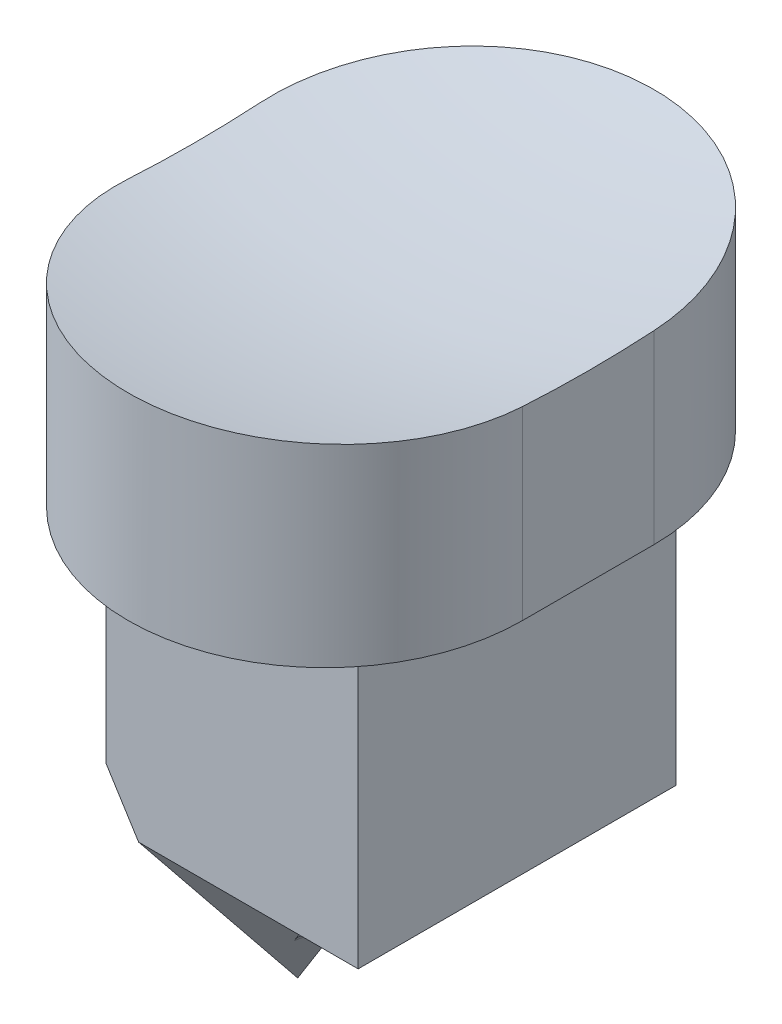
SolidWorks part; units mm, degrees
ref_plane "Front Plane" through (0, 0, 0) normal (0, 0, 1) x (1, 0, 0)
ref_plane "Top Plane" through (0, 0, 0) normal (0, 1, 0) x (1, 0, 0)
ref_plane "Right Plane" through (0, 0, 0) normal (1, 0, 0) x (0, 0, -1)
sketch "Sketch1" plane through (0, 0, 0) normal (0, 1, 0) x (1, 0, 0)
  line L1 (-9.6, 12.1) -> (9.6, 12.1)
  line L2 (-9.6, 12.1) -> (-9.6, -12.1)
  line L3 (-9.6, -12.1) -> (9.6, -12.1)
  line L4 (9.6, 12.1) -> (9.6, -12.1)
  line L5 (-9.6, 12.1) -> (9.6, -12.1) construction
  line L6 (-9.6, -12.1) -> (9.6, 12.1) construction
  point P0 (0, 0)
  dimension "D1" = 19.2
  dimension "D2" = 24.2
extrude "Boss-Extrude1" add sketch "Sketch1" along normal blind 22.1
sketch "Sketch2" plane through (0, 22.1, 0) normal (0, 1, 0) x (1, 0, 0)
  line L0 (0, 5) -> (0, -5) construction
  line L1 (15, 5) -> (15, -5)
  line L2 (-15, 5) -> (-15, -5)
  line L3 (0, 20) -> (0, -20) construction
  line L4 (-9.6, 0) -> (9.6, 0) construction
  line L5 (-9.6, 12.1) -> (-9.6, -12.1) construction
  line L6 (9.6, -12.1) -> (9.6, 12.1) construction
  arc A0 (15, 5) -> (-15, 5) centre (0, 5) ccw
  arc A1 (-15, -5) -> (15, -5) centre (0, -5) ccw
  point P3 (0, 0)
  dimension "D1" = 30
  dimension "D2" = 40
extrude "Boss-Extrude2" add sketch "Sketch2" along normal blind 15
sketch "Sketch4" plane through (-9.6, 0, 0) normal (-1, 0, 0) x (0, 0, 1)
  line L0 (0, 0) -> (0, -15) construction
  line L1 (-12.1, 0) -> (0, -15)
  line L2 (0, -15) -> (12.1, 0)
  line L3 (12.1, 0) -> (-12.1, 0)
  dimension "D1" = 15
extrude "Boss-Extrude3" add sketch "Sketch4" against normal blind 5
sketch "Sketch6" plane through (0, 0, 0) normal (0, 0, 1) x (1, 0, 0)
  line L0 (-4.6, -10) -> (9.6, 0)
  line L3 (-4.6, -10) -> (-4.6, 0)
  line L4 (-4.6, 0) -> (9.6, 0)
  point P2 (-4.6, -15)
  point P3 (-4.6, -11.8258)
  point P5 (-4.6, -5)
  point P9 (-4.6, -15)
  dimension "D1" = 5
extrude "Boss-Extrude4" add sketch "Sketch6" along normal mid plane 3
chamfer "Chamfer1" distance 2.5 angle 45 4 edges at (-9.6, -7.5, -6.05) (-9.6, -7.5, 6.05) (-4.6, -7.5, -6.05) (-4.6, -7.5, 6.05)
fillet "Fillet1" radius 3 2 edges at (-4.6, 0, -5.194) (-4.6, 0, 5.194)
sketch "Sketch8" plane through (0, 0, 0) normal (1, 0, 0) x (0, 0, -1)
  line L0 (-85.2784, 120) -> (85.2784, 120) construction
  line L1 (-85.2784, 120) -> (85.2784, 120)
  line L2 (0, 120) -> (0, 34.7216) construction
  arc A0 (-85.2784, 120) -> (85.2784, 120) centre (0, 120) ccw
  dimension "D1" = 120
revolve "Cut-Revolve3" cut sketch "Sketch8" angle 360 about L1
sketch "Sketch9" plane through (0, 22.1, 0) normal (0, -1, 0) x (1, 0, 0)
  line L4 (9.6, -12.1) -> (-9.6, -12.1) construction
  line L5 (-9.6, -12.1) -> (-9.6, 12.1) construction
  line L6 (-9.6, 12.1) -> (9.6, 12.1) construction
  line L7 (9.6, 12.1) -> (9.6, -12.1) construction
  line L8 (9.6, -12.1) -> (-9.6, -12.1)
  line L9 (-9.6, -12.1) -> (-9.6, 12.1)
  line L10 (-9.6, 12.1) -> (9.6, 12.1)
  line L11 (9.6, 12.1) -> (9.6, -12.1)
extrude "Cut-Extrude-Thin1" cut sketch "Sketch9" against normal blind 10 thin thin type one direction wall 0.3
sketch "Sketch10" plane through (-9.6, 0, 0) normal (-1, 0, 0) x (0, 0, 1)
  line L0 (-12.4, 32.1) -> (12.4, 32.1) construction
  line L1 (-12.4, 32.1) -> (12.4, 32.1)
  line L2 (-12.4, 32.1) -> (-12.4, 32.4)
  line L3 (-12.4, 32.4) -> (12.4, 32.4)
  line L4 (12.4, 32.1) -> (12.4, 32.4)
  line L5 (-12.4, 32.1) -> (-12.4, 22.1) construction
  dimension "D1" = 0.3
extrude "Cut-Extrude1" cut sketch "Sketch10" against normal up to surface (19.2 mm away) up to face at (9.6, 10.7, 0)
sketch "Sketch12" plane through (0, 32.1, 0) normal (0, -1, 0) x (1, 0, 0)
  line L1 (-9.9, 12.4) -> (9.9, 12.4)
  line L2 (-9.9, 12.4) -> (-9.9, -12.4)
  line L3 (-9.9, -12.4) -> (9.9, -12.4)
  line L4 (9.9, 12.4) -> (9.9, -12.4)
extrude "Cut-Extrude3" cut sketch "Sketch12" against normal up to surface (0.3 mm away) up to face at (0, 32.4, 0)
chamfer "Chamfer2" distance 0.75 angle 45 4 edges at (0, 22.1, -12.4) (9.9, 22.1, 0) (0, 22.1, 12.4) (-9.9, 22.1, 0)
chamfer "Chamfer3" distance 0.75 angle 45 4 edges at (0, 32.1, -12.1) (-9.6, 32.1, 0) (0, 32.1, 12.1) (9.6, 32.1, 0)
fillet "Fillet2" radius 1 3 edges at (-4.6, -10, 0) (-5.0734, -10.3334, 1.1607) (-5.0734, -10.3334, -1.1607)
equation "\"Hole Length\"= 25"
equation "\"Hole Height\"= 20"
equation "\"Shell Thickness\"= 5"
equation "\"Can Diameter\"= 66.3"
equation "\"Hole Tolerance\"= 0.8"
equation "\"D1@Sketch1\"=\"Hole Height\"-\"Hole Tolerance\""
equation "\"D2@Sketch1\"=\"Hole Length\"-\"Hole Tolerance\""
equation "\"D1@Sketch2\"=\"Hole Height\"+10"
equation "\"D2@Sketch2\"=\"Hole Length\"+15"
equation "\"D1@Boss-Extrude1\"=\"Shell Thickness\"+17.1"
equation "\"Blade thickness\"= 5"
equation "\"D1@Boss-Extrude3\"=\"Blade thickness\""
